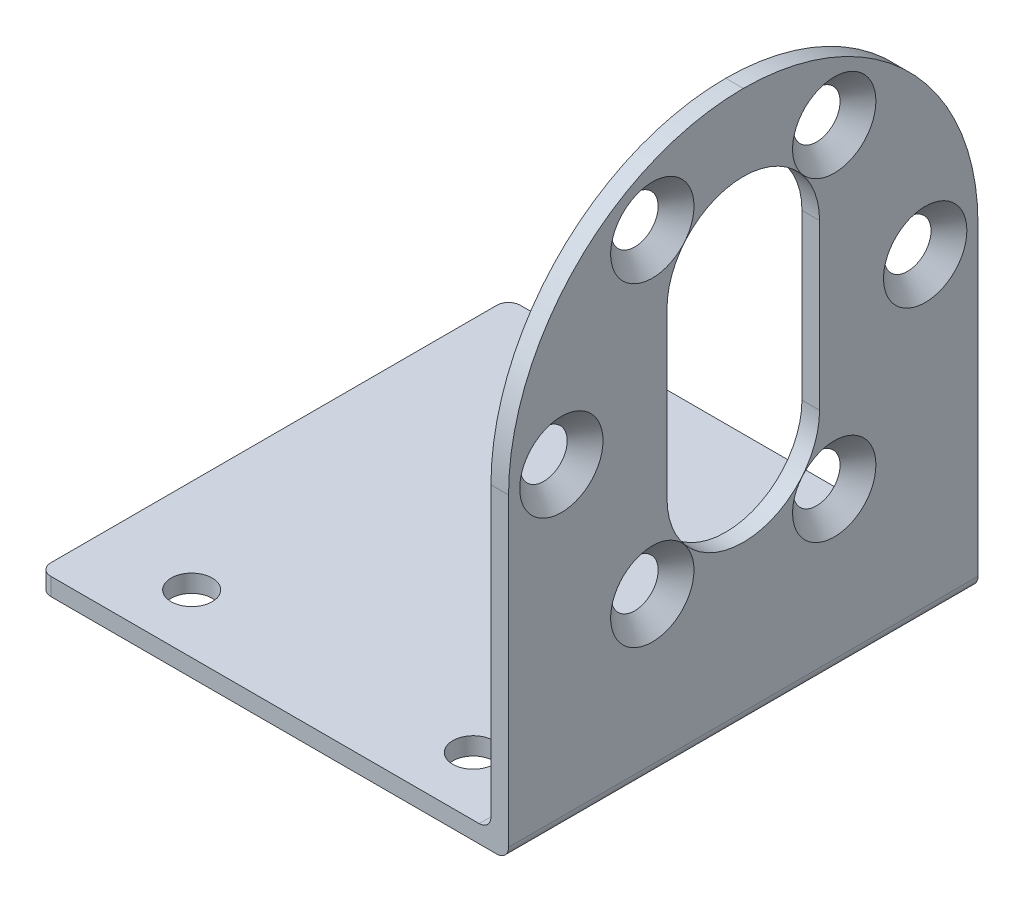
SolidWorks part; units mm, degrees
ref_plane "정면" through (0, 0, 0) normal (0, 0, 1) x (1, 0, 0)
ref_plane "윗면" through (0, 0, 0) normal (0, 1, 0) x (1, 0, 0)
ref_plane "우측면" through (0, 0, 0) normal (1, 0, 0) x (0, 0, -1)
sketch "스케치1" plane through (0, 0, 0) normal (0, 1, 0) x (1, 0, 0)
  line L1 (-20, -20) -> (20, -20)
  line L2 (-20, -20) -> (-20, 20)
  line L3 (-20, 20) -> (20, 20)
  line L4 (20, -20) -> (20, 20)
  line L5 (-20, -20) -> (20, 20) construction
  line L6 (-20, 20) -> (20, -20) construction
  point P0 (0, 0)
  dimension "D1" = 40
  dimension "D2" = 40
extrude "보스-돌출1" add sketch "스케치1" along normal blind 1.5
sketch "스케치2" plane through (0, 1.5, 0) normal (0, 1, 0) x (1, 0, 0)
  line L1 (-12, 15) -> (12, 15) construction
  line L2 (-12, 15) -> (-12, -15) construction
  line L3 (-12, -15) -> (12, -15) construction
  line L4 (12, 15) -> (12, -15) construction
  line L5 (-12, 15) -> (12, -15) construction
  line L6 (-12, -15) -> (12, 15) construction
  line L7 (-20, 0) -> (20, 0) construction
  line L8 (-20, 20) -> (-20, -20) construction
  line L9 (20, -20) -> (20, 20) construction
  circle A0 centre (-12, 15) radius 1.75
  circle A1 centre (12, 15) radius 1.75
  circle A2 centre (-12, -15) radius 1.75
  circle A3 centre (12, -15) radius 1.75
  point P0 (0, 0)
  dimension "D4" = 3.5
  dimension "D1" = 24
  dimension "D2" = 30
  dimension "D3" = 8
extrude "컷-돌출1" cut sketch "스케치2" against normal through all
sketch "스케치3" plane through (0, 1.5, 0) normal (0, 1, 0) x (1, 0, 0)
  line L0 (-20, -20) -> (20, -20) construction
  line L1 (20, 20) -> (18.5, 20)
  line L2 (20, 20) -> (20, -20)
  line L3 (20, -20) -> (18.5, -20)
  line L4 (18.5, 20) -> (18.5, -20)
  dimension "D1" = 1.5
extrude "보스-돌출2" add sketch "스케치3" along normal blind 47 from surface starting at face at (12, 0, -13.25)
sketch "스케치4" plane through (20, 0, 0) normal (1, 0, 0) x (0, 0, -1)
  line L0 (20, 47) -> (-20, 47) construction
  line L1 (0, 20) -> (0, 34) construction
  line L2 (-6.5, 20) -> (-6.5, 34)
  line L3 (6.5, 20) -> (6.5, 34)
  circle A0 centre (0, 27) radius 15.5 construction
  circle A1 centre (15.5, 27) radius 1.5
  circle A2 centre (7.75, 13.5766) radius 1.5
  circle A3 centre (0, 27) radius 15.5 construction
  circle A4 centre (-7.75, 13.5766) radius 1.5
  circle A5 centre (0, 27) radius 15.5 construction
  circle A6 centre (-15.5, 27) radius 1.5
  circle A7 centre (0, 27) radius 15.5 construction
  circle A8 centre (-7.75, 40.4234) radius 1.5
  circle A9 centre (0, 27) radius 15.5 construction
  circle A10 centre (7.75, 40.4234) radius 1.5
  circle A11 centre (0, 27) radius 15.5 construction
  arc A12 (-6.5, 20) -> (6.5, 20) centre (0, 20) ccw
  arc A13 (6.5, 34) -> (-6.5, 34) centre (0, 34) ccw
  point P23 (0, 27)
  point P25 (0, 27)
  point P30 (0, 0)
  dimension "D1" = 20
  dimension "D2" = 31
  dimension "D3" = 3
  dimension "D6" = 6.5
  dimension "D5" = 14
  dimension "D4" = 6
extrude "컷-돌출2" cut sketch "스케치4" against normal through all
sketch "스케치5" plane through (20, 0, 0) normal (1, 0, 0) x (0, 0, -1)
  point P0 (15.5, 27)
  point P3 (7.75, 40.4234)
  point P6 (-7.75, 40.4234)
  point P9 (-15.5, 27)
  point P12 (-7.75, 13.5766)
  point P15 (7.75, 13.5766)
hole_wizard "M3 둥근 십자머리 나사용 카운터싱크1" positions "스케치5" profile "스케치6" countersink size "M3" standard "KS"
sketch "스케치6" plane through (20, 27, -15.5) normal (0, 1, 0) x (0, 0, -1)
  line L0 (0, 0) -> (0, 16.0215)
  line L1 (0, 16.0215) -> (1.7, 15)
  line L2 (1.7, 15) -> (1.7, 1.7865)
  line L3 (1.7, 1.7865) -> (3.55, 0)
  line L5 (3.55, 0) -> (0, 0)
  line L6 (-1.7, 1.7865) -> (-3.55, 0) construction
  line L10 (0, 16.0215) -> (-1.7, 15) construction
  line L11 (0, -6.35) -> (0, 107.95) construction
  dimension "구멍 지름" = 3.4
  dimension "구멍 깊이" = 15
  dimension "표면 카운터싱크 지름" = 7.1
  dimension "표면 카운터싱크 각도" = 92
  dimension "드릴 각도" = 118
fillet "필렛1" radius 20 2 edges at (19.25, 47, -20) (19.25, 47, 20)
fillet "필렛2" radius 1 4 edges at (18.5, 1.5, 0) (20, 0, 0) (-20, 0.75, -20) (-20, 0.75, 20)
